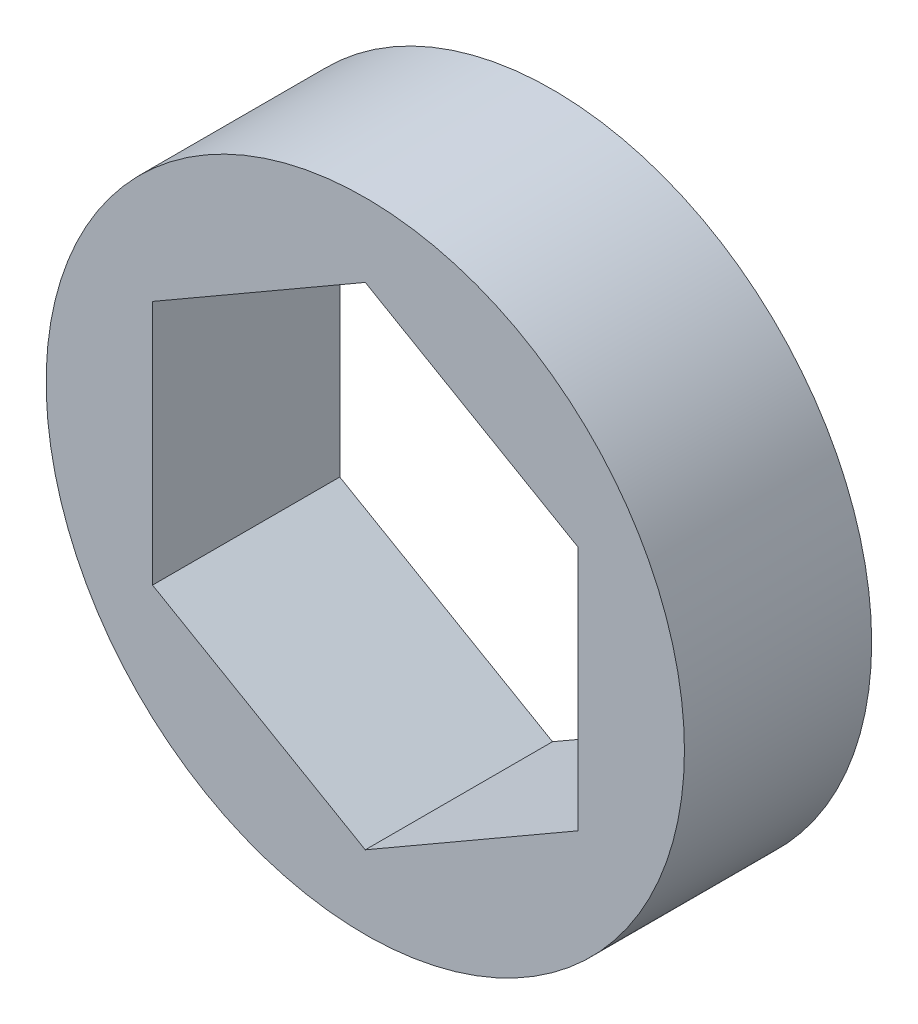
SolidWorks part; units mm, degrees
material "Nylon 101"
ref_plane "Front Plane" through (0, 0, 0) normal (0, 0, 1) x (1, 0, 0)
ref_plane "Top Plane" through (0, 0, 0) normal (0, 1, 0) x (1, 0, 0)
ref_plane "Right Plane" through (0, 0, 0) normal (1, 0, 0) x (0, 0, -1)
sketch "Sketch1" plane through (0, 0, 0) normal (0, 0, 1) x (1, 0, 0)
  line L1 (0, 7.3323) -> (-6.35, 3.6662)
  line L2 (-6.35, 3.6662) -> (-6.35, -3.6662)
  line L3 (-6.35, -3.6662) -> (0, -7.3323)
  line L4 (0, -7.3323) -> (6.35, -3.6662)
  line L5 (6.35, -3.6662) -> (6.35, 3.6662)
  line L6 (6.35, 3.6662) -> (0, 7.3323)
  circle A0 centre (0, 0) radius 9.525
  circle A1 centre (0, 0) radius 6.35 construction
  dimension "D1" = 12.7
  dimension "D2" = 19.05
extrude "Boss-Extrude1" add sketch "Sketch1" along normal blind 5.588
